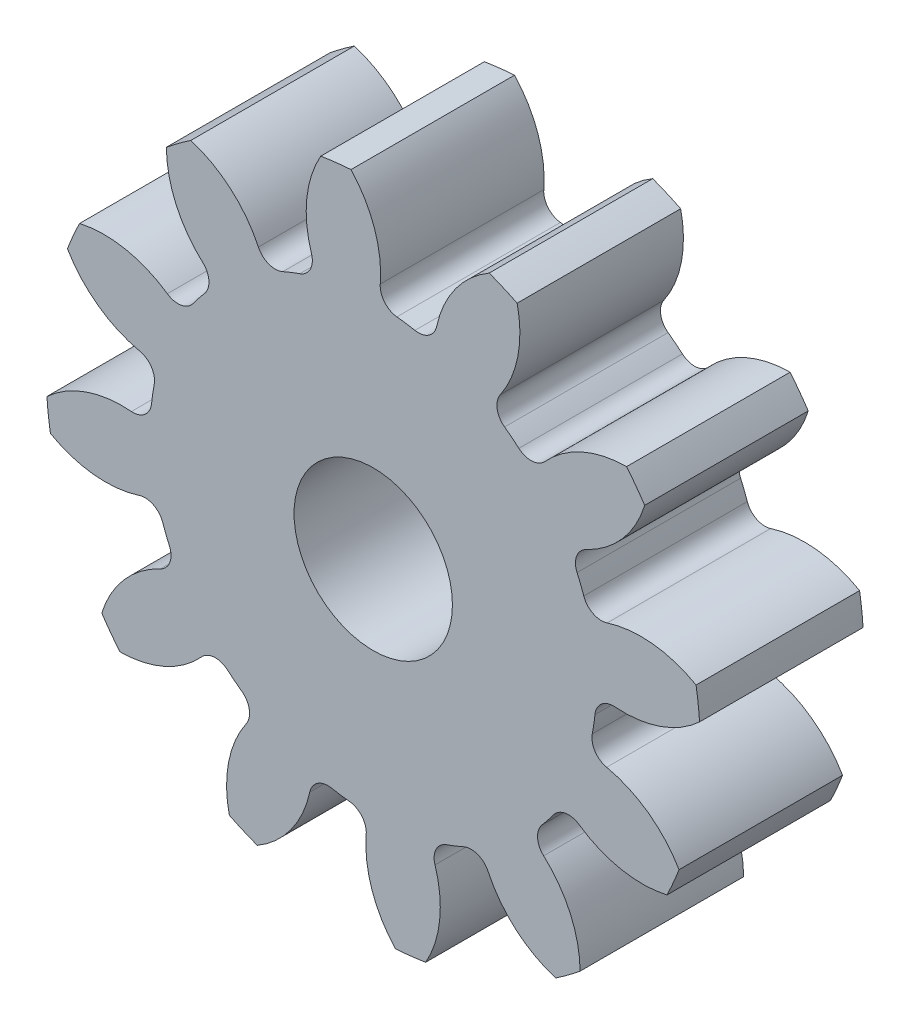
SolidWorks part; units mm, degrees
ref_plane "Front" through (0, 0, 0) normal (0, 0, 1) x (1, 0, 0)
ref_plane "Top" through (0, 0, 0) normal (0, 1, 0) x (1, 0, 0)
ref_plane "Right" through (0, 0, 0) normal (1, 0, 0) x (0, 0, -1)
sketch "Sketch3" plane through (0, 0, 0) normal (0, 0, 1) x (1, 0, 0)
  circle A0 centre (0, 0) radius 12.7
  dimension "od" = 25.4
extrude "gearBody" add sketch "Sketch3" along normal blind 6.35
sketch "Sketch2" plane through (0, 0, 0) normal (0, 0, 1) x (1, 0, 0)
  line L0 (0, 0) -> (9.7367, 4.0331) construction
  line L1 (12.2684, -5.3917) -> (0, 0) construction
  line L2 (0, 0) -> (36.3143, 0) construction
  line L3 (10.8849, -0.1309) -> (10.4544, -3.0337) construction
  line L5 (10.6697, -1.5823) -> (0, 0) construction
  line L7 (0, 0) -> (10.539, 0) construction
  arc A0 (10.5369, -0.2115) -> (10.1448, -2.8555) centre (0, 0) ccw construction
  arc A1 (12.6706, 0.8631) -> (11.8749, -4.5031) centre (0, 0) ccw construction
  arc A2 (10.8849, -0.1309) -> (10.4544, -3.0337) centre (0, 0) ccw construction
  arc A3 (8.505, -1.6194) -> (8.6089, -0.9186) centre (0, 0) ccw
  arc A4 (12.2684, -5.3917) -> (9.0639, -2.4643) centre (8.1472, -6.6852) ccw
  arc A5 (12.2684, -5.3917) -> (13.3051, 1.5993) centre (0, 0) ccw
  arc A6 (13.3051, 1.5993) -> (9.389, -0.2722) centre (9.7367, 4.0331) cw
  arc A7 (8.6089, -0.9186) -> (9.389, -0.2722) centre (9.3305, -0.9956) cw
  arc A8 (9.0639, -2.4643) -> (8.505, -1.6194) centre (9.2179, -1.7551) cw
  point P6 (13.3051, 1.5993)
  point P22 (12.2684, -5.3917)
  dimension "baseDia" = 21.078
  dimension "od" = 25.4
  dimension "pd" = 21.7714
  dimension "rd" = 17.3155
  dimension "rFillet" = 0.7257
  dimension "pointX" = 13.3051
  dimension "pointY" = 1.5993
  dimension "CTT" = 2.9029
  dimension "flankCenterAngle" = 22.5
extrude "toothCut" cut sketch "Sketch2" along normal through all
pattern_circular "CirPattern1" count 12 over 360 about axis through (0, 0, 6.35) along (0, 0, -1) of "toothCut"
ref_axis "toothSpace" through (0, 0, 0) along (0.9892, -0.1467, 0)
ref_axis "Axis2" through (11.6524, -5.051, 0) along (-0.9175, 0.3977, 0)
sketch "hub1Dia" plane through (0, 0, 0) normal (0, 0, -1) x (-1, 0, 0)
  circle A0 centre (0, 0) radius 12.7
  dimension "hub1Dia" = 25.4
sketch "hub2Dia" plane through (0, 0, 6.35) normal (0, 0, 1) x (1, 0, 0)
  circle A0 centre (0, 0) radius 12.7
  dimension "hub2dia" = 25.4
sketch "boreDia" plane through (0, 0, 0) normal (0, 0, 1) x (1, 0, 0)
  circle A0 centre (0, 0) radius 3.075
  dimension "boreDia" = 6.15
extrude "bore" cut sketch "boreDia" against normal mid plane 25400
sketch "kwy1sketch" plane through (0, 0, 0) normal (0, 0, 1) x (1, 0, 0)
  line L0 (-5.8056, 1.9352) -> (0, 0) construction
  line L1 (30.4018, 3.2528) -> (22.3695, -20.8437)
  line L2 (22.3695, -20.8437) -> (-7.7511, -10.8032)
  line L3 (30.4018, 3.2528) -> (0.2812, 13.2933)
  line L4 (-7.7511, -10.8032) -> (0, 0)
  line L5 (0, 0) -> (0.2812, 13.2933)
  line L6 (0, 0) -> (8.5641, -1.27) construction
  line L7 (26.3857, -8.7954) -> (0, 0) construction
  arc A7 (8.505, -1.6194) -> (8.6089, -0.9186) centre (0, 0) ccw construction
  point P9 (26.3857, -8.7954)
  point P13 (-0.9684, 0.3228)
  dimension "kwy1width" = 25.4
  dimension "kwy1depth" = 27.813
  dimension "kwy1angle" = 10
  dimension "kwy1Depth2" = 31.75
sketch "kwy2sketch" plane through (0, 0, 0) normal (0, 0, 1) x (1, 0, 0)
  line L0 (8.5641, -1.27) -> (0, 0) construction
  line L1 (0, 0) -> (-3.7824, -1.8912) construction
  line L2 (19.1973, 23.7974) -> (30.5563, 1.0789)
  line L3 (30.5563, 1.0789) -> (2.1582, -13.1199)
  line L4 (19.1973, 23.7974) -> (-9.2009, 9.5986)
  line L5 (2.1582, -13.1199) -> (0, 0)
  line L6 (0, 0) -> (-9.2009, 9.5986)
  arc A2 (8.505, -1.6194) -> (8.6089, -0.9186) centre (0, 0) ccw construction
  point P10 (24.8768, 12.4382)
  dimension "kwy2angle" = 35
  dimension "kwy2Width" = 25.4
  dimension "kwy2depth" = 27.813
  dimension "kwy2Depth2" = 31.75
sketch "kwy3sketch" plane through (0, 0, 0) normal (0, 0, 1) x (1, 0, 0)
  line L0 (8.5641, -1.27) -> (0, 0) construction
  line L1 (0, 0) -> (-0.9675, -2.9024) construction
  line L2 (-3.2528, 30.4018) -> (20.8437, 22.3695)
  line L3 (20.8437, 22.3695) -> (10.8032, -7.7511)
  line L4 (-3.2528, 30.4018) -> (-13.2933, 0.2812)
  line L5 (10.8032, -7.7511) -> (0, 0)
  line L6 (-13.2933, 0.2812) -> (0, 0)
  point P10 (8.7954, 26.3857)
  dimension "kwy3angle" = 80
  dimension "kwy3depth" = 27.813
  dimension "kwy3width" = 25.4
  dimension "kwy3Depth2" = 31.75
sketch "kwy4sketch" plane through (0, 0, 0) normal (0, 0, 1) x (1, 0, 0)
  line L0 (8.5641, -1.27) -> (0, 0) construction
  line L1 (0, 0) -> (1.0698, -2.1396) construction
  line L2 (-1.0789, 30.5563) -> (-23.7974, 19.1973)
  line L3 (-23.7974, 19.1973) -> (-9.5986, -9.2009)
  line L4 (-9.5986, -9.2009) -> (0, 0)
  line L5 (13.1199, 2.1582) -> (0, 0)
  line L6 (-1.0789, 30.5563) -> (13.1199, 2.1582)
  point P15 (-12.4382, 24.8768)
  dimension "kwy4angle" = 125
  dimension "kwy4depth" = 27.813
  dimension "kwy4width" = 25.4
  dimension "kwy4Depth2" = 31.75
sketch "kwy5sketch" plane through (0, 0, 0) normal (0, 0, 1) x (1, 0, 0)
  line L0 (8.5641, -1.27) -> (0, 0) construction
  line L1 (0, 0) -> (1.949, -0.6497) construction
  line L2 (-22.3695, 20.8437) -> (-30.4018, -3.2528)
  line L3 (-30.4018, -3.2528) -> (-0.2812, -13.2933)
  line L4 (-22.3695, 20.8437) -> (7.7511, 10.8032)
  line L5 (-0.2812, -13.2933) -> (0, 0)
  line L6 (7.7511, 10.8032) -> (0, 0)
  point P10 (-26.3857, 8.7954)
  dimension "kwy5width" = 25.4
  dimension "kwy5depth" = 27.813
  dimension "kwy5angle" = 170
  dimension "kwy5Depth2" = 31.75
sketch "kwy6sketch" plane through (0, 0, 0) normal (0, 0, 1) x (1, 0, 0)
  line L0 (8.5641, -1.27) -> (0, 0) construction
  line L1 (0, 0) -> (1.8361, 0.918) construction
  line L2 (-30.5563, -1.0789) -> (-19.1973, -23.7974)
  line L3 (-19.1973, -23.7974) -> (9.2009, -9.5986)
  line L4 (-30.5563, -1.0789) -> (-2.1582, 13.1199)
  line L5 (9.2009, -9.5986) -> (0, 0)
  line L6 (-2.1582, 13.1199) -> (0, 0)
  point P10 (-24.8768, -12.4382)
  dimension "kwy6angle" = 215
  dimension "kwy6width" = 25.4
  dimension "kwy6depth" = 27.813
  dimension "kwy6Depth2" = 31.75
sketch "kwy7sketch" plane through (0, 0, 0) normal (0, 0, 1) x (1, 0, 0)
  line L0 (8.5641, -1.27) -> (0, 0) construction
  line L1 (0, 0) -> (0.7273, 2.1818) construction
  line L2 (-20.8437, -22.3695) -> (3.2528, -30.4018)
  line L3 (-20.8437, -22.3695) -> (-10.8032, 7.7511)
  line L4 (3.2528, -30.4018) -> (13.2933, -0.2812)
  line L5 (-10.8032, 7.7511) -> (0, 0)
  line L6 (13.2933, -0.2812) -> (0, 0)
  point P10 (-8.7954, -26.3857)
  dimension "kwy7angle" = 80
  dimension "kwy7width" = 25.4
  dimension "kwy7depth" = 27.813
  dimension "kwy7angle1" = 260
  dimension "kwy7Depth2" = 31.75
sketch "kwy8sketch" plane through (0, 0, 0) normal (0, 0, 1) x (1, 0, 0)
  line L0 (8.5641, -1.27) -> (0, 0) construction
  line L1 (0, 0) -> (-0.9138, 1.8276) construction
  line L2 (1.0789, -30.5563) -> (23.7974, -19.1973)
  line L3 (23.7974, -19.1973) -> (9.5986, 9.2009)
  line L4 (1.0789, -30.5563) -> (-13.1199, -2.1582)
  line L5 (9.5986, 9.2009) -> (0, 0)
  line L6 (-13.1199, -2.1582) -> (0, 0)
  point P10 (12.4382, -24.8768)
  dimension "kwy8angle" = 305
  dimension "kwy8width" = 25.4
  dimension "kwy8depth" = 27.813
  dimension "kwy8Depth2" = 31.75
sketch "centerLine" plane through (0, 0, 0) normal (0, 1, 0) x (1, 0, 0)
  line L0 (0, 36.4807) -> (0, -59.6309) construction
ref_plane "CB1plane" through (0, 0, 0) normal (0, 0, -1) x (-1, 0, 0)
sketch "CB1diameter" plane through (0, 0, 0) normal (0, 0, -1) x (-1, 0, 0)
  circle A0 centre (0, 0) radius 12.7
  dimension "CB1diameter" = 25.4
ref_plane "CB2plane" through (0, 0, 6.35) normal (0, 0, 1) x (1, 0, 0)
sketch "CB2diameter" plane through (0, 0, 6.35) normal (0, 0, 1) x (1, 0, 0)
  circle A0 centre (0, 0) radius 12.7
  dimension "CB2diameter" = 25.4
ref_axis "Axis1" through (0, 0, 50) along (0, 0, -1)
